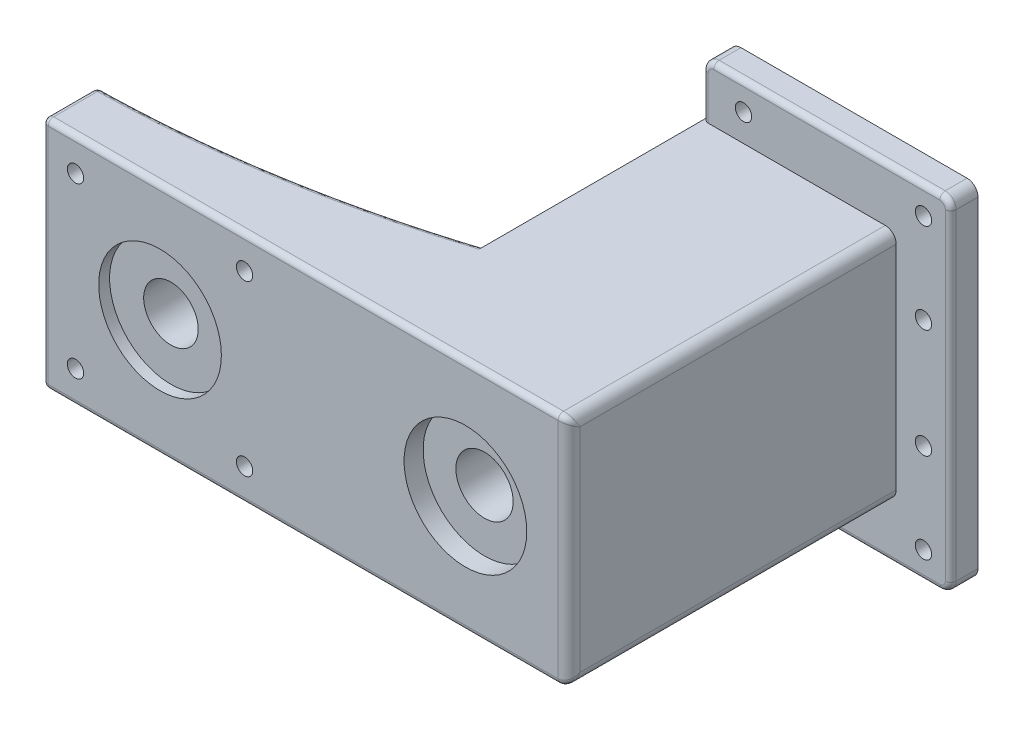
SolidWorks part; units mm, degrees
ref_plane "Front" through (0, 0, 0) normal (0, 0, 1) x (1, 0, 0)
ref_plane "Top" through (0, 0, 0) normal (0, 1, 0) x (1, 0, 0)
ref_plane "Right" through (0, 0, 0) normal (1, 0, 0) x (0, 0, -1)
sketch "Sketch1" plane through (0, 0, 0) normal (0, 0, 1) x (1, 0, 0)
  line L2 (-21.5, 21.5) -> (21.5, 21.5)
  line L3 (-21.5, 21.5) -> (-21.5, -21.5)
  line L4 (-21.5, -21.5) -> (21.5, -21.5)
  line L8 (75, 0) -> (75, 21.5)
  line L9 (75, 21.5) -> (21.5, 21.5)
  line L10 (75, 0) -> (75, -21.5)
  line L11 (75, -21.5) -> (21.5, -21.5)
extrude "Boss-Extrude1" add sketch "Sketch1" along normal blind 10
sketch "Sketch2" plane through (0, 0, 10) normal (0, 0, 1) x (1, 0, 0)
  circle A0 centre (0, 0) radius 5
  circle A1 centre (-15.5, 15.5) radius 1.5
  circle A2 centre (15.5, 15.5) radius 1.5
  circle A3 centre (15.5, -15.5) radius 1.5
  circle A4 centre (-15.5, -15.5) radius 1.5
  point P0 (0, 0)
extrude "Cut-Extrude1" cut sketch "Sketch2" against normal blind 10
sketch "Sketch3" plane through (0, 0, 10) normal (0, 0, 1) x (1, 0, 0)
  circle A0 centre (0, 0) radius 11.25
extrude "Cut-Extrude2" cut sketch "Sketch3" against normal blind 2
sketch "Sketch4" plane through (0, 0, 10) normal (0, 0, 1) x (1, 0, 0)
  circle A0 centre (56, 0) radius 5.25
extrude "Cut-Extrude3" cut sketch "Sketch4" against normal blind 10
sketch "Sketch5" plane through (0, 0, 10) normal (0, 0, 1) x (1, 0, 0)
  circle A0 centre (56, 0) radius 11.25
extrude "Cut-Extrude4" cut sketch "Sketch5" against normal blind 3.5
sketch "Sketch6" plane through (0, 0, 0) normal (0, 0, -1) x (-1, 0, 0)
  line L0 (-56, 11) -> (-43.6348, 11)
  line L2 (-43.6348, -11) -> (-56, -11)
  line L3 (-39.5316, 21.5) -> (-75, 21.5)
  line L4 (-75, 21.5) -> (21.5, 21.5) construction
  line L5 (-75, 21.5) -> (-75, -21.5)
  line L6 (-75, -21.5) -> (-39.5316, -21.5)
  arc A0 (-39.5316, 21.5) -> (-43.6348, 11) centre (0, 0) ccw
  arc A1 (-56, 11) -> (-56, -11) centre (-56, 0) ccw
  arc A2 (-43.6348, -11) -> (-39.5316, -21.5) centre (0, 0) ccw
extrude "Boss-Extrude2" add sketch "Sketch6" along normal blind 55
sketch "Sketch7" plane through (0, -21.5, 0) normal (0, -1, 0) x (1, 0, 0)
  line L1 (39.5316, -55) -> (39.5316, 0) construction
  line L2 (39.5316, -10) -> (75, -10)
  line L3 (75, 10) -> (75, -55) construction
  line L4 (75, -10) -> (75, 0)
  line L5 (75, 0) -> (39.5316, 0)
  line L6 (39.5316, 0) -> (39.5316, -10)
extrude "Boss-Extrude3" add sketch "Sketch7" against normal blind 43
sketch "Sketch8" plane through (0, -21.5, 0) normal (0, -1, 0) x (1, 0, 0)
  line L0 (39.5316, -10) -> (39.5316, 0)
  line L1 (39.5316, 0) -> (-21.5, 0)
  spline S0 degree 2 poles (39.5316, -10) (9.3845, -0.4695) (-21.5, 0) knots 0 0 0 0.906099 0.906099 0.906099
extrude "Boss-Extrude4" add sketch "Sketch8" against normal blind 43
sketch "Sketch10" plane through (0, 0, 10) normal (0, 0, 1) x (1, 0, 0)
  circle A0 centre (0, 0) radius 5
  circle A1 centre (15.5, -15.5) radius 1.5
  circle A2 centre (-15.5, -15.5) radius 1.5
  circle A3 centre (-15.5, 15.5) radius 1.5
  circle A4 centre (15.5, 15.5) radius 1.5
extrude "Cut-Extrude5" cut sketch "Sketch10" against normal blind 43
sketch "Sketch11" plane through (0, 0, -10) normal (0, 0, -1) x (-1, 0, 0)
  circle A0 centre (-15.5, 15.5) radius 1.5001
  circle A1 centre (15.5, 15.5) radius 1.5
  circle A2 centre (-15.5, -15.5) radius 1.5
  circle A3 centre (15.5, -15.5) radius 1.5
  circle A4 centre (0, 0) radius 10
extrude "Cut-Extrude6" cut sketch "Sketch11" against normal blind 10
sketch "Sketch12" plane through (0, 0, -55) normal (0, 0, -1) x (-1, 0, 0)
  line L2 (-75, -31.5) -> (-85, -31.5)
  line L3 (-85, -31.5) -> (-85, 31.5)
  line L4 (-39.5316, 21.5) -> (-39.5316, 31.5)
  line L5 (-39.5316, 31.5) -> (-85, 31.5)
  line L6 (-39.5316, -21.5) -> (-39.5316, -31.5)
  line L7 (-39.5316, -31.5) -> (-75, -31.5)
  arc A0 (-39.5316, 21.5) -> (-39.5316, -21.5) centre (0, 0) ccw
extrude "Boss-Extrude6" add sketch "Sketch12" against normal blind 5
sketch "Sketch13" plane through (0, 0, 6.5) normal (0, 0, 1) x (1, 0, 0)
  circle A0 centre (56, 0) radius 5.25
extrude "Cut-Extrude7" cut sketch "Sketch13" against normal blind 100
sketch "Sketch14" plane through (0, 0, -55) normal (0, 0, -1) x (-1, 0, 0)
  circle A1 centre (-56, 8) radius 1.5
  circle A2 centre (-64, 0) radius 1.5
  circle A3 centre (-56, -8) radius 1.5
  circle A4 centre (-48, 0) radius 1.5
extrude "Cut-Extrude8" cut sketch "Sketch14" against normal blind 10
sketch "Sketch15" plane through (0, 0, -50) normal (0, 0, 1) x (1, 0, 0)
  line L2 (81.434, 9.5599) -> (81.5, 10) construction
  line L7 (78.5, -10) -> (78.566, -9.5599) construction
  line L8 (78.5, 10) -> (78.566, 9.5599) construction
  line L10 (81.434, -9.5599) -> (81.5, -10) construction
  circle A0 centre (80, -26.5) radius 1.5
  circle A1 centre (80, 26.5) radius 1.5
  circle A2 centre (80, -10) radius 1.5
  circle A3 centre (80, 10) radius 1.5
  point P10 (80, 0)
extrude "Cut-Extrude9" cut sketch "Sketch15" against normal blind 10
sketch "Sketch16" plane through (0, 0, -50) normal (0, 0, 1) x (1, 0, 0)
  circle A0 centre (47.0016, 26.5) radius 1.5
  circle A1 centre (47.0016, -26.5) radius 1.5
extrude "Cut-Extrude10" cut sketch "Sketch16" against normal blind 10
sketch "Sketch18" plane through (0, 0, -10) normal (0, 0, -1) x (-1, 0, 0)
  circle A0 centre (-15.5, 15.5) radius 3
  circle A1 centre (15.5, 15.5) radius 3
  circle A2 centre (15.5, -15.5) radius 3
  circle A3 centre (-15.5, -15.5) radius 3
extrude "Cut-Extrude11" cut sketch "Sketch18" against normal blind 10
fillet "Fillet1" radius 2 7 edges at (39.5316, 31.5, -52.5) (39.5316, -31.5, -52.5) (85, 31.5, -52.5) (85, -31.5, -52.5) (75, -21.5, -20) (75, 0, 10) (75, 21.5, -20)
fillet "Fillet2" radius 1 10 edges at (74.4142, -20.9142, 9.4142) (74.4142, 20.9142, 9.4142) (-21.5, 21.5, 5) (-21.5, 0, 0) (-21.5, 0, 10) (25.75, -21.5, 10) (-21.5, -21.5, 5) (25.75, 21.5, 10)
fillet "Fillet3" radius 1 9 edges at (39.5316, 25.5, -50) (40.1174, 30.9142, -50) (62.2658, 31.5, -50) (84.4142, 30.9142, -50) (39.5316, -25.5, -50) (40.1174, -30.9142, -50) (62.2658, -31.5, -50) (84.4142, -30.9142, -50) (85, 0, -50)
